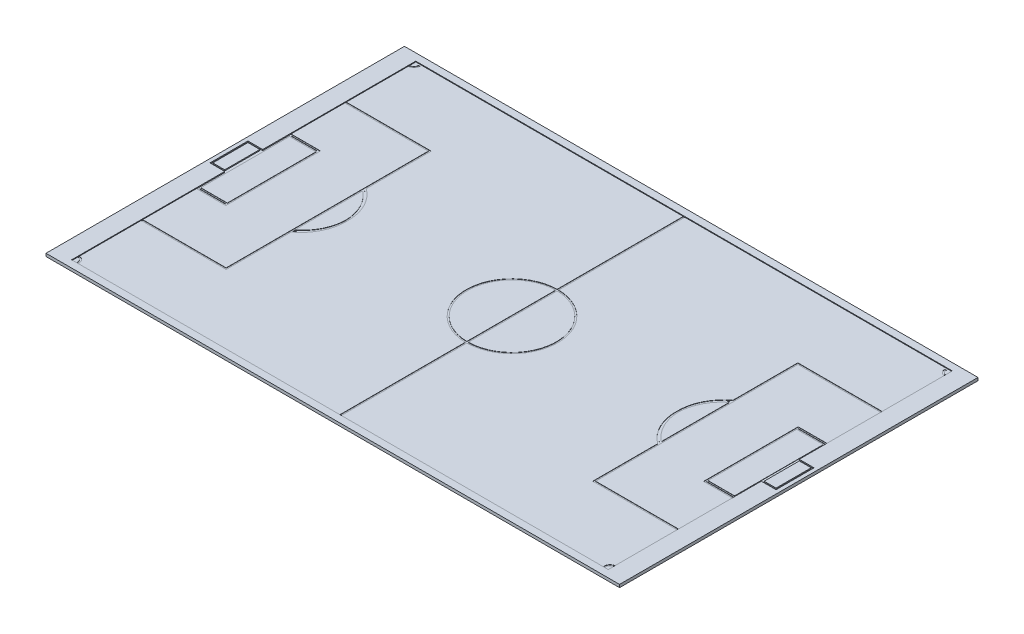
SolidWorks part; units mm, degrees
ref_plane "前基準面" through (0, 0, 0) normal (0, 0, 1) x (1, 0, 0)
ref_plane "上基準面" through (0, 0, 0) normal (0, 1, 0) x (1, 0, 0)
ref_plane "右基準面" through (0, 0, 0) normal (1, 0, 0) x (0, 0, -1)
sketch "草圖1" plane through (0, 0, 0) normal (0, 1, 0) x (1, 0, 0)
  line L1 (-2000, -1250) -> (2000, -1250)
  line L2 (-2000, -1250) -> (-2000, 1250)
  line L3 (-2000, 1250) -> (2000, 1250)
  line L4 (2000, -1250) -> (2000, 1250)
  line L5 (-2000, -1250) -> (2000, 1250) construction
  line L6 (-2000, 1250) -> (2000, -1250) construction
  point P0 (0, 0)
  dimension "D1" = 4000
  dimension "D2" = 2500
extrude "填料-伸長1" add sketch "草圖1" along normal blind 20
sketch "草圖3" plane through (0, 20, 0) normal (0, 1, 0) x (1, 0, 0)
  line L0 (-1868.4543, 1189.2136) -> (-1868.4543, -1199.9271)
  line L5 (-1868.4543, -1199.9271) -> (1871.0702, -1199.9271)
  line L6 (1871.0702, -1199.9271) -> (1871.0702, 1189.2136)
  line L7 (1871.0702, 1189.2136) -> (-1868.4543, 1189.2136)
extrude "除料-伸長1" cut sketch "草圖3" against normal blind 5
sketch "草圖4" plane through (0, 15, 0) normal (0, 1, 0) x (1, 0, 0)
  line L0 (-1868.4543, 715) -> (-1288.4543, 715)
  line L1 (-1868.4543, 1189.2136) -> (-1868.4543, -1199.9271) construction
  line L2 (-1868.4543, 705) -> (-1288.4543, 705)
  line L3 (2000, 1250) -> (-2000, 1250) construction
  line L4 (-1288.4543, 715) -> (-1278.4543, 715)
  line L5 (-1278.4543, 715) -> (-1278.4543, -715)
  line L6 (-1278.4543, -715) -> (-1868.4543, -715)
  line L7 (-1868.4543, -715) -> (-1868.4543, -705)
  line L8 (-1868.4543, 1189.2136) -> (-1868.4543, -1199.9271) construction
  line L9 (-1868.4543, -705) -> (-1288.4543, -705)
  line L10 (-1288.4543, -705) -> (-1288.4543, 705)
  line L11 (-1868.4543, 715) -> (-1868.4543, 705)
  line L14 (-2000, -1250) -> (2000, -1250) construction
  dimension "D1" = 580
  dimension "D3" = 535
  dimension "D4" = 10
  dimension "D5" = 535
  dimension "D6" = 10
  dimension "D2" = 10
extrude "除料-伸長3" cut sketch "草圖4" against normal blind 2 contours L6 L7 L9 L10 L2 L11 L0 L4 L5
sketch "草圖5" plane through (0, 15, 0) normal (0, 1, 0) x (1, 0, 0)
  line L0 (1871.0702, -1199.9271) -> (1871.0702, 1189.2136) construction
  line L1 (1666.0702, 319.2136) -> (1871.0702, 319.2136)
  line L2 (1666.0702, 319.2136) -> (1666.0702, -329.9271)
  line L3 (1666.0702, -329.9271) -> (1871.0702, -329.9271)
  line L4 (1871.0702, 319.2136) -> (1871.0702, -329.9271)
  line L5 (1666.0702, 319.2136) -> (1871.0702, -329.9271) construction
  line L6 (1666.0702, -329.9271) -> (1871.0702, 319.2136) construction
  line L7 (1871.0702, -1199.9271) -> (1871.0702, 1189.2136) construction
  line L8 (1871.0702, 1189.2136) -> (-1868.4543, 1189.2136) construction
  line L9 (-1868.4543, -1199.9271) -> (1871.0702, -1199.9271) construction
  line L10 (1676.0702, 309.2136) -> (1676.0702, -319.9271)
  line L11 (1676.0702, -319.9271) -> (1861.0702, -319.9271)
  line L12 (1861.0702, 309.2136) -> (1861.0702, -319.9271)
  line L13 (1676.0702, 309.2136) -> (1861.0702, 309.2136)
  line L14 (2000, 1250) -> (-2000, 1250) construction
  line L15 (1871.0702, 132.5) -> (1974.0702, 132.5)
  line L16 (1871.0702, 132.5) -> (1871.0702, -132.5)
  line L17 (1871.0702, -132.5) -> (1974.0702, -132.5)
  line L18 (1974.0702, 132.5) -> (1974.0702, -132.5)
  line L19 (1871.0702, 132.5) -> (1974.0702, -132.5) construction
  line L20 (1871.0702, -132.5) -> (1974.0702, 132.5) construction
  line L21 (1964.0702, 122.5) -> (1964.0702, -122.5)
  line L22 (1881.0702, -122.5) -> (1964.0702, -122.5)
  line L23 (1881.0702, 122.5) -> (1881.0702, -122.5)
  line L24 (1881.0702, 122.5) -> (1964.0702, 122.5)
  point P0 (1768.5702, -5.3567)
  point P15 (1922.5702, 0)
  line M15 (1871.0702, -1199.9271) -> (1871.0702, 1189.2136)
  dimension "D1" = 870
  dimension "D2" = 205
  dimension "D3" = 870
  dimension "D5" = 103
  dimension "D6" = 265
  dimension "D7" = 1250
  dimension "D4" = 10
  dimension "D8" = 10
extrude "除料-伸長5" cut sketch "草圖5" against normal blind 2 contours L2 L3 L4 L1 L10 L13 L12 L11 M15 | L18 L15 L4 L17 L23 L24 L21 L22 region at (1768.5702, 15, -312.4062) region at (1922.5702, 15, -129.6569)
sketch "草圖7" plane through (0, 20, 0) normal (0, 1, 0) x (1, 0, 0)
  line L4 (1676.0702, 309.2136) -> (1676.0702, -319.9271)
  line L5 (1676.0702, -319.9271) -> (1861.0702, -319.9271)
  line L6 (1861.0702, -319.9271) -> (1861.0702, 309.2136)
  line L7 (1861.0702, 309.2136) -> (1676.0702, 309.2136)
  line L8 (1676.0702, 309.2136) -> (1676.0702, -319.9271)
  line L9 (1676.0702, -319.9271) -> (1861.0702, -319.9271)
  line L10 (1861.0702, -319.9271) -> (1861.0702, 309.2136)
  line L11 (1861.0702, 309.2136) -> (1676.0702, 309.2136)
  line L12 (1871.0702, 319.2136) -> (1666.0702, 319.2136)
  line L13 (1871.0702, -329.9271) -> (1871.0702, 319.2136)
  line L14 (1666.0702, -329.9271) -> (1871.0702, -329.9271)
  line L15 (1666.0702, 319.2136) -> (1666.0702, -329.9271)
  line L16 (1871.0702, 319.2136) -> (1666.0702, 319.2136)
  line L17 (1871.0702, -329.9271) -> (1871.0702, 319.2136)
  line L18 (1666.0702, -329.9271) -> (1871.0702, -329.9271)
  line L19 (1666.0702, 319.2136) -> (1666.0702, -329.9271)
  line L20 (1964.0702, -122.5) -> (1964.0702, 122.5)
  line L21 (1881.0702, -122.5) -> (1964.0702, -122.5)
  line L22 (1881.0702, 122.5) -> (1881.0702, -122.5)
  line L23 (1964.0702, 122.5) -> (1881.0702, 122.5)
  line L24 (1964.0702, -122.5) -> (1964.0702, 122.5)
  line L25 (1881.0702, -122.5) -> (1964.0702, -122.5)
  line L26 (1881.0702, 122.5) -> (1881.0702, -122.5)
  line L27 (1964.0702, 122.5) -> (1881.0702, 122.5)
  line L28 (1974.0702, 132.5) -> (1871.0702, 132.5)
  line L29 (1974.0702, -132.5) -> (1974.0702, 132.5)
  line L30 (1871.0702, -132.5) -> (1974.0702, -132.5)
  line L31 (1871.0702, 132.5) -> (1871.0702, -132.5)
  line L32 (1974.0702, 132.5) -> (1871.0702, 132.5)
  line L33 (1974.0702, -132.5) -> (1974.0702, 132.5)
  line L34 (1871.0702, -132.5) -> (1974.0702, -132.5)
  line L35 (1871.0702, 132.5) -> (1871.0702, -132.5)
  dimension "D1" = 0
  dimension "D2" = 0
  dimension "D3" = 0
  dimension "D4" = 0
extrude "除料-伸長6" cut sketch "草圖7" against normal blind 5 contours L17 L34 L33 L32 L27 L24 L25 L26 region at (1922.5702, 20, -129.6569)
sketch "草圖8" plane through (0, 15, 0) normal (0, 1, 0) x (1, 0, 0)
  circle A0 centre (-1481.1119, -6.1657) radius 18.8939
  circle A1 centre (-1481.1119, -6.1657) radius 12.3863
sketch "草圖9" plane through (0, 15, 0) normal (0, 1, 0) x (1, 0, 0)
  line L0 (-1868.4543, -1199.9271) -> (1871.0702, -1199.9271) construction
  line L1 (5, 1199.9271) -> (-5, 1199.9271)
  line L2 (5, 1199.9271) -> (5, -1199.9271)
  line L3 (5, -1199.9271) -> (-5, -1199.9271)
  line L4 (-5, 1199.9271) -> (-5, -1199.9271)
  line L5 (5, 1199.9271) -> (-5, -1199.9271) construction
  line L6 (5, -1199.9271) -> (-5, 1199.9271) construction
  line L8 (-1278.4543, 715) -> (-1278.4543, -715) construction
  line L9 (-1278.4543, 715) -> (-1278.4543, -715) construction
  line L11 (-1278.4543, 249.3702) -> (-1278.4543, 236.8293)
  line L12 (-1278.4543, -249.9447) -> (-1278.4543, -262.4856)
  line L13 (1871.0702, 1189.2136) -> (-1868.4543, 1189.2136) construction
  line L14 (-1868.4543, 1189.2136) -> (-1868.4543, -1199.9271) construction
  line L15 (-1841.1219, 1188.6214) -> (-1831.1395, 1189.2136)
  line L16 (-1869.0465, 1157.175) -> (-1868.4543, 1147.1925)
  circle A0 centre (0, 0) radius 320
  circle A1 centre (0, 0) radius 310
  arc A2 (-1278.4543, 249.3702) -> (-1278.4543, -262.4856) centre (-1467.3586, -6.5577) cw
  arc A4 (-1278.4543, 236.8293) -> (-1278.4543, -249.9447) centre (-1467.3586, -6.5577) cw
  arc A5 (-1284.393, 241.3246) -> (-1284.393, -254.44) centre (-1467.3586, -6.5577) cw construction
  arc A6 (-1831.1395, 1189.2136) -> (-1868.4543, 1147.1925) centre (-1870.8075, 1186.8605) cw
  arc A7 (-1841.1219, 1188.6214) -> (-1869.0465, 1157.175) centre (-1870.8075, 1186.8605) cw
  line M11 (1871.0702, 1189.2136) -> (-1868.4543, 1189.2136)
  line M12 (-1868.4543, 1189.2136) -> (-1868.4543, 715)
  line M14 (-1278.4543, 715) -> (-1278.4543, -715)
  line M17 (-1868.4543, -1199.9271) -> (1871.0702, -1199.9271)
  dimension "D2" = 10
  dimension "D3" = 640
  dimension "D1" = 10
  dimension "D4" = 10
  dimension "D5" = 10
extrude "除料-伸長16" cut sketch "草圖9" against normal blind 2 contours A4 A2 M14 region at (-1154.5434, 15, 6.5577)
extrude "除料-伸長17" cut sketch "草圖9<3>" against normal blind 2 contours A1 L2 A0 | A1 L4 A0 | A1 L2 A0 L4 | A1 L4 A0 L2 region at (222.9524, 15, -219.4956) region at (0, 15, -314.9868) region at (-12.1325, 15, -314.9603) region at (0, 15, 314.9868)
sketch "草圖9<3>" plane through (0, 15, 0) normal (0, 1, 0) x (1, 0, 0) same geometry as "草圖9"
extrude "除料-伸長18" cut sketch "草圖9<4>" against normal blind 2 contours A0 L2 L4 M11 | A0 L4 L2 M17 | L2 A1 L4 | L15 A7 A6 M12 region at (-1847.1436, 15, -1166.0168) region at (0, 15, -754.6003) region at (0, 15, 0) region at (0, 15, 759.957)
sketch "草圖9<4>" plane through (0, 15, 0) normal (0, 1, 0) x (1, 0, 0) same geometry as "草圖9"
mirror "鏡射1" about plane through (0, 0, 0) normal (1, 0, 0) of "除料-伸長5", "除料-伸長1", "除料-伸長18", "除料-伸長17", "除料-伸長16", "除料-伸長3", "除料-伸長6"
mirror "鏡射3" about plane through (0, 0, 0) normal (0, 0, 1) of "鏡射1"
